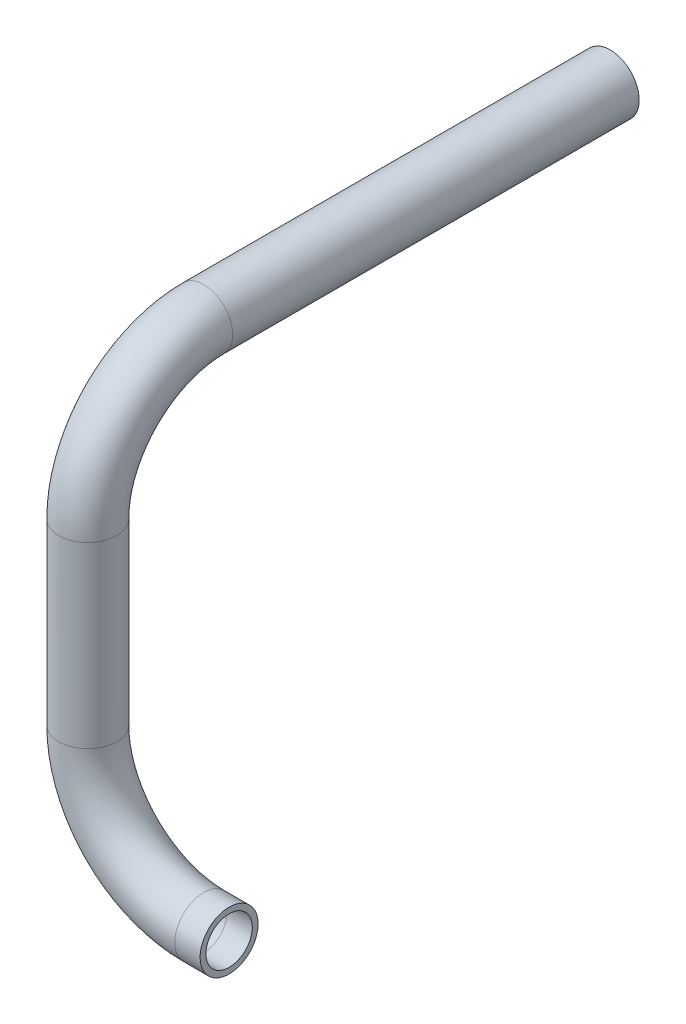
SolidWorks part; units mm, degrees
material "Silicon Rubber"
ref_plane "Front" through (0, 0, 0) normal (0, 0, 1) x (1, 0, 0)
ref_plane "Top" through (0, 0, 0) normal (0, 1, 0) x (1, 0, 0)
ref_plane "Right" through (0, 0, 0) normal (1, 0, 0) x (0, 0, -1)
ref_axis "Axis1" through (0, 0, 55) along (0, 0, -1)
sketch3d "3DSketch1"
  line L0 (-267.546, 126.2764, 20.5596) -> (-267.546, 126.2764, 109.5641)
  line L1 (-236.5936, 36.3764, 134.9641) -> (-242.146, 36.3764, 134.9641)
  line L2 (-267.546, 100.8764, 134.9641) -> (-267.546, 61.7764, 134.9641)
  arc A0 (-267.546, 100.8764, 134.9641) -> (-267.546, 126.2764, 109.5641) centre (-267.546, 100.8764, 109.5641) ccw
  arc A1 (-242.146, 36.3764, 134.9641) -> (-267.546, 61.7764, 134.9641) centre (-242.146, 61.7764, 134.9641) ccw
  point P6 (-292.946, 100.8764, 109.5641)
  point P9 (-242.146, 61.7764, 109.5641)
  dimension "D1" = 89.0045
ref_plane "Plane1" through (-267.546, 126.2764, 20.5596) normal (0, 0, 1) x (1, 0, 0)
sketch "Sketch1" plane through (-267.546, 126.2764, 20.5596) normal (0, 0, 1) x (1, 0, 0)
  circle A0 centre (0, 0) radius 6.35
  circle A1 centre (0, 0) radius 5.08
  dimension "D1" = 12.7
  dimension "D2" = 10.16
sweep "Sweep1" add profiles "Sketch1" path "3DSketch1"
